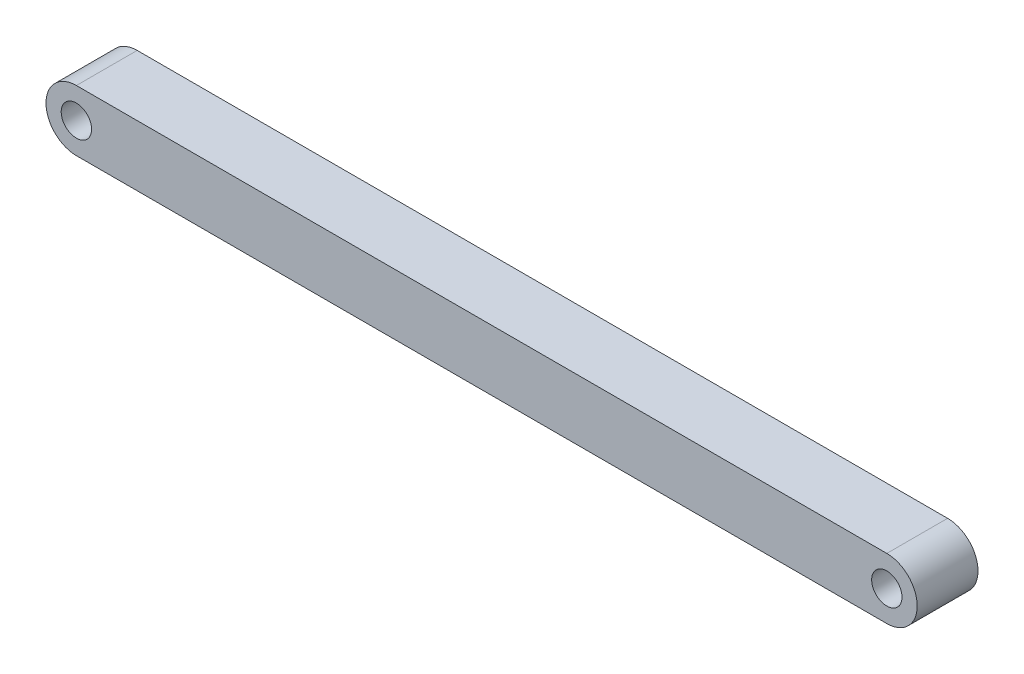
SolidWorks part; units mm, degrees
ref_plane "Plan de face" through (0, 0, 0) normal (0, 0, 1) x (1, 0, 0)
ref_plane "Plan de dessus" through (0, 0, 0) normal (0, 1, 0) x (1, 0, 0)
ref_plane "Plan de droite" through (0, 0, 0) normal (1, 0, 0) x (0, 0, -1)
sketch "Esquisse1" plane through (0, 0, 0) normal (0, 0, 1) x (1, 0, 0)
  line L0 (0, 0) -> (80, 0) construction
  line L1 (0, 3) -> (80, 3)
  line L2 (0, -3) -> (80, -3)
  arc A0 (0, 3) -> (0, -3) centre (0, 0) ccw
  arc A1 (80, -3) -> (80, 3) centre (80, 0) ccw
  circle A2 centre (0, 0) radius 1.5
  circle A3 centre (80, 0) radius 1.5
  point P3 (40, 0)
  dimension "D1" = 3
  dimension "D2" = 6
  dimension "D3" = 80
extrude "Boss.-Extru.1" add sketch "Esquisse1" along normal blind 3 and the other way blind 3
